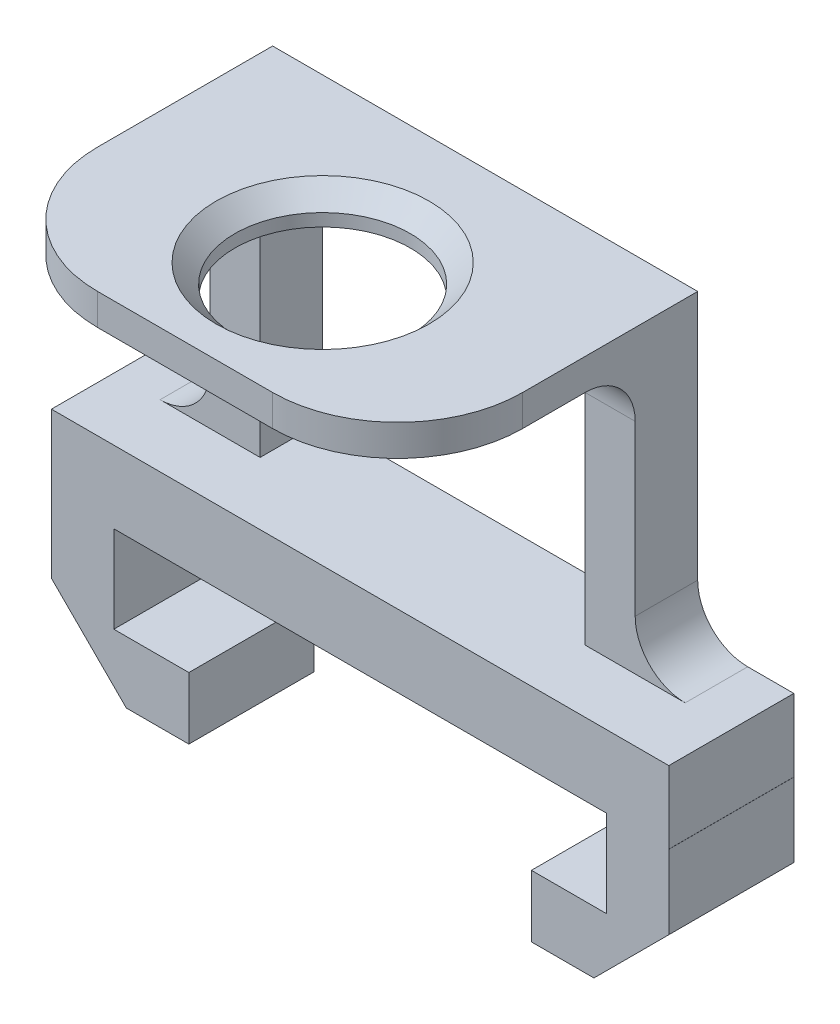
SolidWorks part; units mm, degrees
ref_plane "Front Plane" through (0, 0, 0) normal (0, 0, 1) x (1, 0, 0)
ref_plane "Top Plane" through (0, 0, 0) normal (0, 1, 0) x (1, 0, 0)
ref_plane "Right Plane" through (0, 0, 0) normal (1, 0, 0) x (0, 0, -1)
sketch "Sketch2" plane through (0, 0, 0) normal (0, 0, 1) x (1, 0, 0)
  line L0 (12.3453, 19.45) -> (-12.3453, 19.45)
  line L1 (12.3453, 22.3446) -> (-12.3453, 22.3446)
  line L2 (12.3453, 19.45) -> (12.3453, 22.3446)
  line L8 (-12.3453, 19.45) -> (-12.3453, 22.3446)
  dimension "D2" = 2.8946
extrude "Boss-Extrude2" add sketch "Sketch2" along normal blind 3
extrude "Boss-Extrude3" add sketch "Sketch2<2>" against normal blind 2
sketch "Sketch2<2>" plane through (0, 0, 0) normal (0, 0, 1) x (1, 0, 0) same geometry as "Sketch2"
ref_plane "Plane4" through (0, 0, 3) normal (0, 0, 1) x (1, 0, 0)
ref_plane "Plane6" through (0, 19.45, 0) normal (0, -1, 0) x (-1, 0, 0)
sketch "Sketch8" plane through (0, 19.45, 0) normal (0, -1, 0) x (-1, 0, 0)
  line L1 (-1.592, -3) -> (1.592, -3) construction
  line L2 (12.35, 2) -> (9.85, 2)
  line L3 (12.3453, 2) -> (-12.3453, 2) construction
  line L4 (-9.85, 2) -> (-9.85, -3)
  line L5 (-9.85, -3) -> (-12.35, -3)
  line L6 (-12.35, -3) -> (-12.35, 2)
  line L7 (-12.35, 2) -> (-9.85, 2)
  line L8 (12.35, -3) -> (12.35, 2)
  line L9 (9.85, -3) -> (12.35, -3)
  line L10 (9.85, 2) -> (9.85, -3)
  point P0 (0, 0)
  dimension "D1" = 9.85
  dimension "D2" = 9.85
  dimension "D3" = 2.5
  dimension "D4" = 2.5
  dimension "D5" = 0
extrude "Boss-Extrude4" add sketch "Sketch8" along normal blind 5.96
ref_plane "Plane7" through (9.85, 0, 0) normal (-1, 0, 0) x (0, 0, 1)
sketch "Sketch10" plane through (9.85, 0, 0) normal (-1, 0, 0) x (0, 0, 1)
  line L0 (3, 13.49) -> (-2, 13.49) construction
  line L1 (3, 13.49) -> (-2, 13.49)
  line L2 (3, 13.49) -> (3, 15.97)
  line L3 (3, 15.97) -> (-2, 15.97)
  line L4 (-2, 13.49) -> (-2, 15.97)
  line L5 (-2, 13.49) -> (-2, 19.45) construction
  line L6 (3, 13.49) -> (3, 19.45) construction
  dimension "D1" = 2.48
  dimension "D2" = 0
extrude "Boss-Extrude5" add sketch "Sketch10" along normal blind 3
ref_plane "Plane8" through (-9.85, 0, 0) normal (1, 0, 0) x (0, 0, -1)
sketch "Sketch11" plane through (-9.85, 0, 0) normal (1, 0, 0) x (0, 0, -1)
  line L0 (2, 13.49) -> (2, 19.45) construction
  line L1 (-3, 13.49) -> (2, 13.49)
  line L2 (-3, 13.49) -> (-3, 15.97)
  line L3 (-3, 15.97) -> (2, 15.97)
  line L4 (2, 13.49) -> (2, 15.97)
  dimension "D1" = 2.48
extrude "Boss-Extrude6" add sketch "Sketch11" along normal blind 3
ref_plane "Plane9" through (0, 22.3446, 0) normal (0, 1, 0) x (1, 0, 0)
sketch "Sketch12" plane through (0, 22.3446, 0) normal (0, 1, 0) x (1, 0, 0)
  line L2 (12.3453, 2) -> (-12.3453, 2) construction
  line L5 (8.5, -0.5) -> (8.5, 2)
  line L6 (8.5, 2) -> (-8.5, 2)
  line L7 (-8.5, -0.5) -> (-8.5, 2)
  line L9 (8.5, -0.5) -> (-8.5, -0.5)
  point P6 (0, 0)
  dimension "D1" = 0
  dimension "D2" = 8.5
  dimension "D3" = 2.5
extrude "Boss-Extrude7" add sketch "Sketch12" along normal blind 12
ref_plane "Plane10" through (0, 0, 0.5) normal (0, 0, 1) x (1, 0, 0)
sketch "Sketch14" plane through (0, 0, 0.5) normal (0, 0, 1) x (1, 0, 0)
  line L1 (-8.5, 34.3446) -> (8.5, 34.3446) construction
  line L2 (12.3453, 22.3446) -> (-12.3453, 22.3446) construction
  line L7 (-6.5, 33.0946) -> (6.5, 33.0946)
  line L8 (-6.5, 33.0946) -> (-6.5, 22.3446)
  line L9 (-6.5, 22.3446) -> (6.5, 22.3446)
  line L10 (6.5, 33.0946) -> (6.5, 22.3446)
  dimension "D1" = 1.25
  dimension "D2" = 0
extrude "Cut-Extrude7" cut sketch "Sketch14" against normal up to next
sketch "Sketch16" plane through (0, 0, 0.5) normal (0, 0, 1) x (1, 0, 0)
  line L1 (-8.5, 34.3446) -> (8.5, 34.3446)
  line L2 (-8.5, 34.3446) -> (-8.5, 33.0946)
  line L3 (-8.5, 33.0946) -> (8.5, 33.0946)
  line L4 (8.5, 34.3446) -> (8.5, 33.0946)
  line L5 (-8.5, 34.3446) -> (8.5, 34.3446) construction
  dimension "D1" = 1.25
  dimension "D2" = 0
extrude "Boss-Extrude8" add sketch "Sketch16" along normal blind 9.5
ref_plane "Plane11" through (0, 34.3446, 0) normal (0, 1, 0) x (1, 0, 0)
sketch "Sketch17" plane through (0, 34.3446, 0) normal (0, 1, 0) x (1, 0, 0)
  line L0 (8.5, -10) -> (-8.5, -10) construction
  line L1 (-8.5, 2) -> (-8.5, -10) construction
  circle A0 centre (0, -4.5) radius 3.51
  dimension "D1" = 5.5
  dimension "D2" = 8.5
extrude "Cut-Extrude8" cut sketch "Sketch17" against normal up to next
chamfer "Chamfer1" distance 3 angle 45 1 edges at (-12.35, 13.49, 0.5)
chamfer "Chamfer2" distance 3 angle 45 1 edges at (12.35, 13.49, 0.5)
ref_plane "Plane14" through (-8.5, 0, 0) normal (-1, 0, 0) x (0, 0, 1)
chamfer "Lens Chamfer" distance 0.75 angle 45 1 edges at (0, 34.3446, 8.01)
fillet "Fillet13" radius 2 2 edges at (-7.5, 33.0946, 0.5) (7.5, 33.0946, 0.5)
fillet "Fillet14" radius 2 2 edges
fillet "Fillet15" radius 5 2 edges at (-8.5, 33.7196, 10) (8.5, 33.7196, 10)
